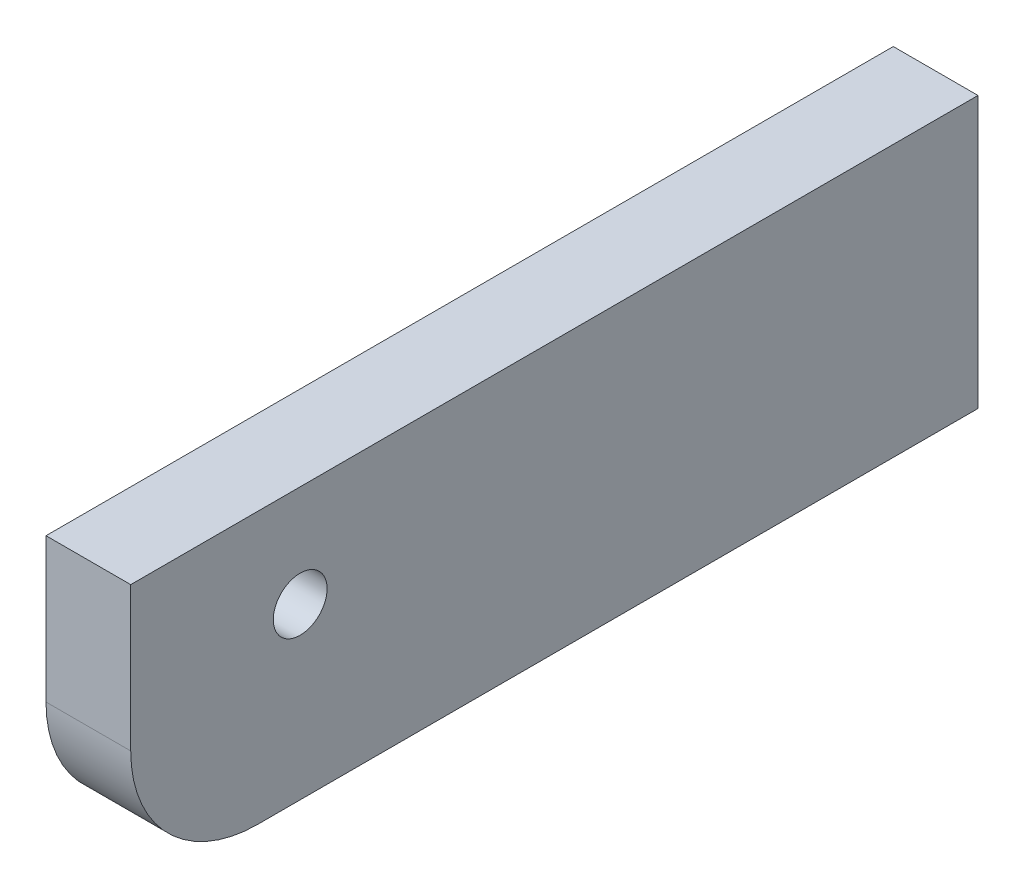
SolidWorks part; units mm, degrees
material "Plain Carbon Steel"
ref_plane "Front Plane" through (0, 0, 0) normal (0, 0, 1) x (1, 0, 0)
ref_plane "Top Plane" through (0, 0, 0) normal (0, 1, 0) x (1, 0, 0)
ref_plane "Right Plane" through (0, 0, 0) normal (1, 0, 0) x (0, 0, -1)
sketch "Sketch1" plane through (0, 0, 0) normal (1, 0, 0) x (0, 0, -1)
  line L1 (-50, -16) -> (50, -16)
  line L2 (-50, -16) -> (-50, 16)
  line L3 (-50, 16) -> (50, 16)
  line L4 (50, -16) -> (50, 16)
  line L5 (-50, -16) -> (50, 16) construction
  line L6 (-50, 16) -> (50, -16) construction
  circle A0 centre (-30, 4) radius 3.175
  point P0 (0, 0)
  dimension "D3" = 6.35
  dimension "D1" = 32
  dimension "D2" = 100
  dimension "D4" = 20
  dimension "D5" = 12
extrude "Boss-Extrude1" add sketch "Sketch1" along normal blind 10 contours L1 L4 L3 L2 A0 | A0 region at (0, -0.04, -0.2999)
fillet "Fillet1" radius 15 1 edges at (5, -16, 50)
